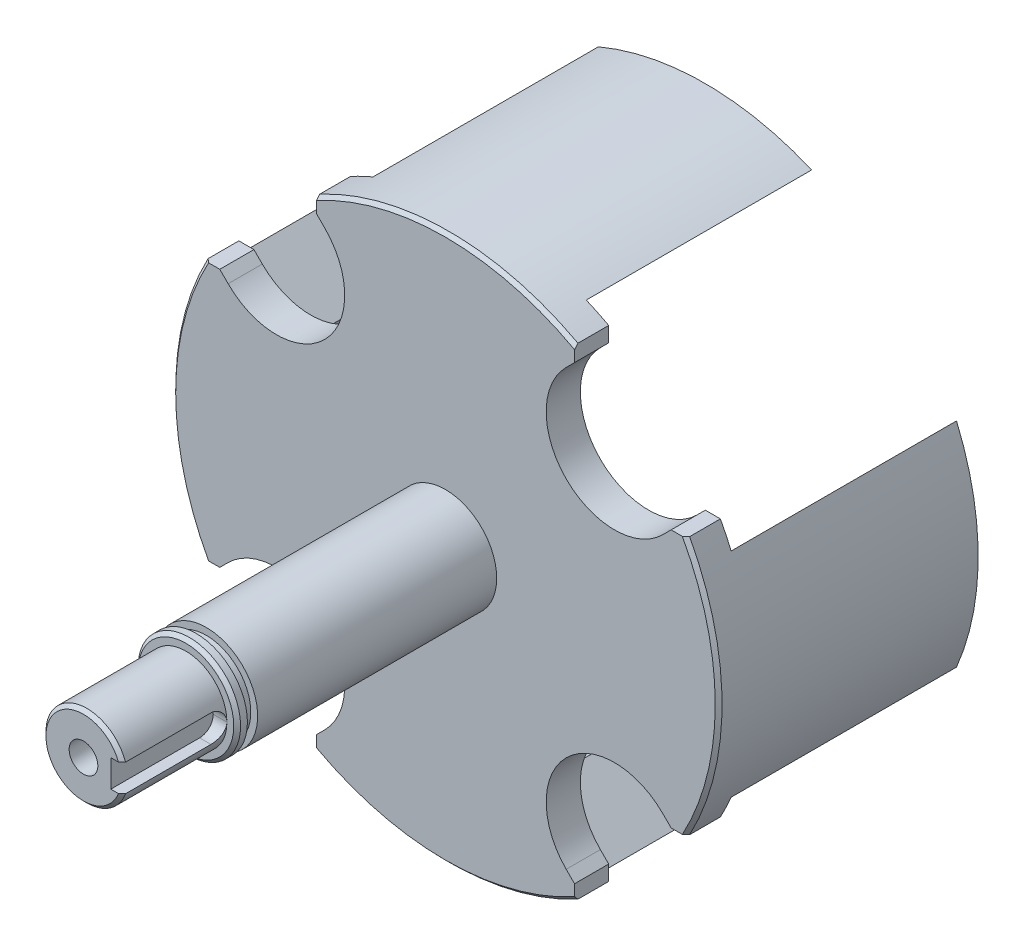
SolidWorks part; units mm, degrees
ref_plane "前视基准面" through (0, 0, 0) normal (0, 0, 1) x (1, 0, 0)
ref_plane "上视基准面" through (0, 0, 0) normal (0, 1, 0) x (1, 0, 0)
ref_plane "右视基准面" through (0, 0, 0) normal (1, 0, 0) x (0, 0, -1)
sketch "草图1" plane through (0, 0, 0) normal (0, 0, 1) x (1, 0, 0)
  circle A0 centre (-62.2771, 0) radius 40
  dimension "D1" = 80
extrude "凸台-拉伸1" add sketch "草图1" along normal blind 5
sketch "草图2" plane through (0, 0, 5) normal (0, 0, 1) x (1, 0, 0)
  circle A0 centre (-62.2771, 0) radius 7.5
  dimension "D1" = 15
extrude "凸台-拉伸2" add sketch "草图2" along normal blind 38
ref_plane "基准面1" through (0, 0, 0) normal (0, -1, 0) x (0, 0, -1)
sketch "草图3" plane through (0, 0, 0) normal (0, -1, 0) x (0, 0, -1)
  line L0 (-23.1701, -62.2771) -> (-60.245, -62.2771) construction
  line L1 (-43, -62.2771) -> (-5, -62.2771) construction
  line L2 (-5, -22.2771) -> (-5, -102.2771) construction
  line L3 (-41.5, -51.3163) -> (-40, -51.3163)
  line L4 (-41.5, -51.3163) -> (-41.5, -55.7771)
  line L5 (-41.5, -55.7771) -> (-40, -55.7771)
  line L6 (-40, -51.3163) -> (-40, -55.7771)
  line L7 (-5, -54.7771) -> (-43, -54.7771) construction
  dimension "D1" = 1.5
  dimension "D2" = 35
  dimension "D3" = 1
revolve "切除-旋转1" cut sketch "草图3" angle 360 about L0
sketch "草图4" plane through (0, 0, 43) normal (0, 0, 1) x (1, 0, 0)
  circle A0 centre (-62.2771, 0) radius 6
  dimension "D1" = 12
extrude "凸台-拉伸3" add sketch "草图4" along normal blind 15
chamfer "倒角1" distance 0.5 angle 45 3 edges at (-22.2771, 0, 5) (-54.7771, 0, 43) (-56.2771, 0, 58)
sketch "草图5" plane through (0, 0, 58) normal (0, 0, 1) x (1, 0, 0)
  line L0 (-19.25, 0) -> (19.25, 0) construction
  line L1 (-58.2771, 2) -> (-50.3846, 2)
  line L2 (-58.2771, 2) -> (-58.2771, -2)
  line L3 (-58.2771, -2) -> (-50.3846, -2)
  line L4 (-50.3846, 2) -> (-50.3846, -2)
  line L5 (-58.2771, 2) -> (-50.3846, -2) construction
  line L6 (-58.2771, -2) -> (-50.3846, 2) construction
  circle A0 centre (-62.2771, 0) radius 5.5 construction
  point P0 (-54.3308, 0)
  dimension "D1" = 4
  dimension "D2" = 4
extrude "切除-拉伸1" cut sketch "草图5" against normal blind 15
fillet "圆角1" radius 2 2 edges at (-57.4486, -2, 43) (-57.4486, 2, 43)
sketch "草图6" plane through (0, 0, 0) normal (0, 0, -1) x (-1, 0, 0)
  circle A0 centre (62.2771, 0) radius 40
  circle A1 centre (62.2771, 0) radius 30
  dimension "D1" = 60
extrude "凸台-拉伸4" add sketch "草图6" along normal blind 33
hole_wizard "M8 螺纹孔1" positions "草图10" profile "草图9" tap size "M8" standard "GB"
sketch "草图10" plane through (0, 0, -33) normal (0, 0, -1) x (-1, 0, 0)
  circle A0 centre (62.2771, 0) radius 30 construction
  circle A1 centre (62.2771, 0) radius 30 construction
  point P0 (97.2771, 0)
  dimension "D1" = 0
  dimension "D2" = 35
sketch "草图9" plane through (-97.2771, 0, -33) normal (1, 0, 0) x (0, 1, 0)
  line L0 (0, 0) -> (0, 21.7929)
  line L1 (0, 21.7929) -> (3.4, 19.75)
  line L2 (3.4, 19.75) -> (3.4, 0)
  line L5 (3.4, 0) -> (0, 0)
  line L10 (0, 21.7929) -> (-3.4, 19.75) construction
  line L11 (0, -6.35) -> (0, 107.95) construction
  dimension "螺纹孔钻头直径" = 6.8
  dimension "螺纹孔钻头深度" = 19.75
  dimension "导头角度" = 118
cosmetic thread "孔螺蚊线1" parameters "D1"=16, "D2"=8
pattern_circular "阵列(圆周)1" count 4 every 90 about axis through (-62.2771, 0, -33) along (0, 0, 1) of "M8 螺纹孔1"
sketch "草图11" plane through (0, 0, -33) normal (0, 0, -1) x (-1, 0, 0)
  line L0 (-32.2671, 73.331) -> (135.608, -94.5442)
  line L1 (-32.2671, 73.331) -> (-11.0539, 94.5442)
  line L2 (135.608, -94.5442) -> (156.8212, -73.331)
  line L3 (-11.0539, 94.5442) -> (156.8212, -73.331)
  line L4 (-32.2671, 73.331) -> (156.8212, -73.331) construction
  line L5 (135.608, -94.5442) -> (-11.0539, 94.5442) construction
  line L6 (62.2771, 0) -> (126.0994, 0) construction
  point P1 (62.2771, 0)
  dimension "D1" = 45
  dimension "D2" = 30
extrude "切除-拉伸2" cut sketch "草图11" against normal blind 33
pattern_circular "阵列(圆周)2" count 2 every 90 about axis through (-62.2771, 0, -33) along (0, 0, 1) of "切除-拉伸2"
sketch "草图12" plane through (0, 0, 0) normal (0, 0, -1) x (-1, 0, 0)
  circle A0 centre (62.2771, 0) radius 8.5
  dimension "D1" = 17
extrude "切除-拉伸3" cut sketch "草图12" against normal blind 2
hole_wizard "M6 螺纹孔1" positions "草图14" profile "草图13" tap size "M6" standard "GB"
sketch "草图14" plane through (0, 0, 2) normal (0, 0, -1) x (-1, 0, 0)
  point P0 (62.2771, 0)
sketch "草图13" plane through (-62.2771, 0, 2) normal (1, 0, 0) x (0, 1, 0)
  line L0 (0, 0) -> (0, 16.5022)
  line L1 (0, 16.5022) -> (2.5, 15)
  line L2 (2.5, 15) -> (2.5, 0)
  line L5 (2.5, 0) -> (0, 0)
  line L10 (0, 16.5022) -> (-2.5, 15) construction
  line L11 (0, -6.35) -> (0, 107.95) construction
  dimension "螺纹孔钻头直径" = 5
  dimension "螺纹孔钻头深度" = 15
  dimension "导头角度" = 118
cosmetic thread "孔螺蚊线2" parameters "D1"=12, "D2"=6
sketch "草图15" plane through (0, 0, 0) normal (0, 0, -1) x (-1, 0, 0)
  line L0 (62.2771, 0) -> (115.3101, 53.033) construction
  line L1 (-19.25, 0) -> (19.25, 0) construction
  line L2 (87.0258, 24.7487) -> (90.5613, 28.2843) construction
  line L3 (79.9547, 31.8198) -> (83.4903, 35.3553)
  line L4 (94.0969, 17.6777) -> (97.6324, 21.2132)
  arc A0 (79.9547, 31.8198) -> (94.0969, 17.6777) centre (87.0258, 24.7487) ccw
  arc A1 (97.6324, 21.2132) -> (83.4903, 35.3553) centre (90.5613, 28.2843) ccw
  circle A2 centre (62.2771, 0) radius 8.5 construction
  point P7 (88.7936, 26.5165)
  dimension "D3" = 10
  dimension "D1" = 135
  dimension "D2" = 35
  dimension "D4" = 5
extrude "切除-拉伸4" cut sketch "草图15" against normal blind 10
pattern_circular "阵列(圆周)3" count 4 every 90 about axis through (-62.2771, 0, 5) along (0, 0, -1) of "切除-拉伸4"
chamfer "倒角2" distance 2 angle 45 8 edges at (-41.962, -34.4572, 2.25) (-27.8199, -20.3151, 2.25) (-27.8199, 20.3151, 2.25) (-41.962, 34.4572, 2.25) (-82.5921, 34.4572, 2.25) (-96.7342, 20.3151, 2.25) (-82.5921, -34.4572, 2.25) (-96.7342, -20.3151, 2.25) first distance on face at (-43.1265, -33.2926, 2.95) first distance on face at (-28.9113, -19.2236, 2.85) first distance on face at (-28.9844, 19.1505, 2.95) first distance on face at (-43.0535, 33.3657, 2.85) first distance on face at (-81.4276, 33.2926, 2.95) first distance on face at (-95.6428, 19.2236, 2.85) first distance on face at (-81.5006, -33.3657, 2.85) first distance on face at (-95.5697, -19.1505, 2.95)
hole_wizard "M5 螺纹孔1" positions "草图17" profile "草图18" tap size "M5" standard "GB"
sketch "草图17" plane through (0, 0, 58) normal (0, 0, 1) x (1, 0, 0)
  point P0 (-62.2771, 0)
sketch "草图18" plane through (-62.2771, 0, 58) normal (1, 0, 0) x (0, -1, 0)
  line L0 (0, 0) -> (0, 13.6618)
  line L1 (0, 13.6618) -> (2.1, 12.4)
  line L2 (2.1, 12.4) -> (2.1, 0)
  line L5 (2.1, 0) -> (0, 0)
  line L10 (0, 13.6618) -> (-2.1, 12.4) construction
  line L11 (0, -6.35) -> (0, 107.95) construction
  dimension "螺纹孔钻头直径" = 4.2
  dimension "螺纹孔钻头深度" = 12.4
  dimension "导头角度" = 118
cosmetic thread "孔螺蚊线3" parameters "D1"=10, "D2"=5
